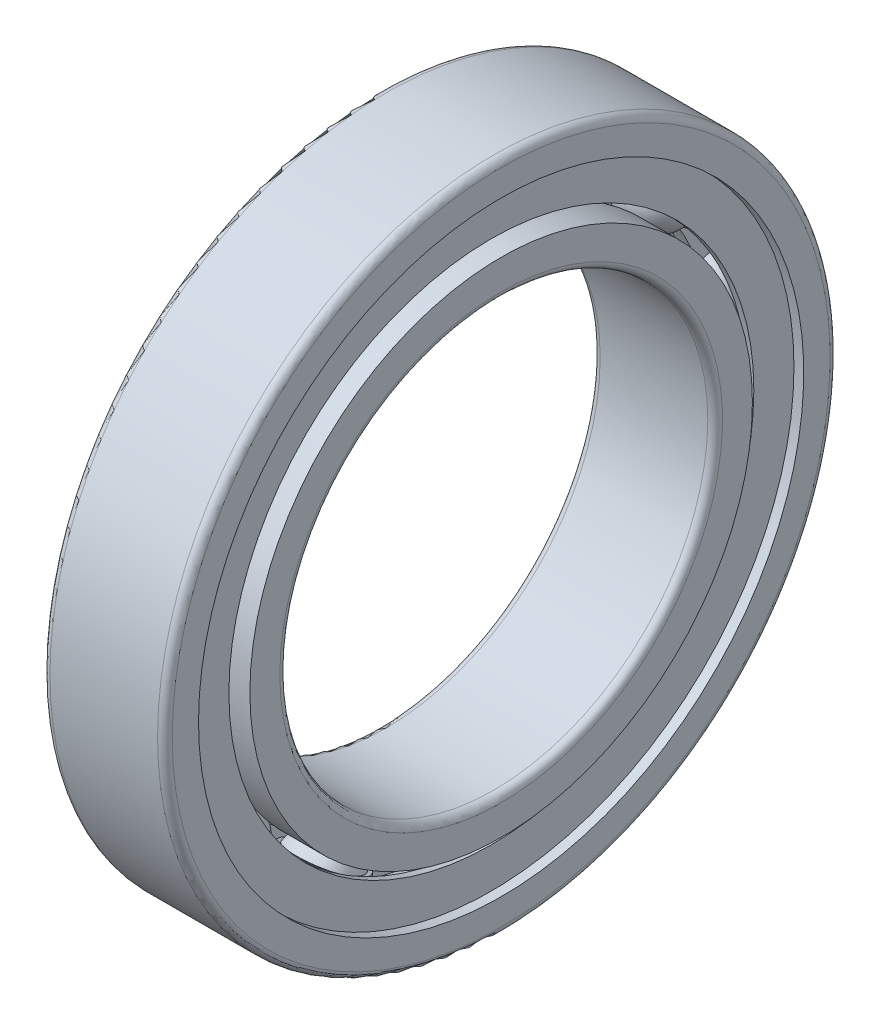
SolidWorks part; units mm, degrees
ref_plane "基准面1" through (0, 0, 0) normal (0, 0, 1) x (1, 0, 0)
ref_plane "基准面2" through (0, 0, 0) normal (0, 1, 0) x (1, 0, 0)
ref_plane "基准面3" through (0, 0, 0) normal (1, 0, 0) x (0, 0, -1)
sketch "尺寸草图" plane through (0, 0, 0) normal (0, 0, 1) x (1, 0, 0)
  point P0 (0, -75.4307)
  point P1 (5.556, -75.4307)
  point P2 (0, 50.7088)
  point P3 (35, 50.7088)
  point P4 (55, 50.7088)
  point P5 (10, 50.7088)
  point P6 (0, -10.9899)
  point P7 (41.1, -10.9899)
  point P8 (50.3, -10.9899)
  point P9 (0.6, -10.9899)
  point P10 (14, -75.4307)
  dimension "d" = 35
  dimension "DD" = 55
  dimension "B" = 10
  dimension "内圈外径DD2" = 41.1
  dimension "防尘圈径D3" = 50.3
  dimension "r" = 0.6
  dimension "球径DW" = 5.556
  dimension "球数Z" = 14
sketch "草图2" plane through (0, 0, 0) normal (0, 0, 1) x (1, 0, 0)
  line L0 (-12.4206, 0) -> (9.8128, 0) construction
  line L1 (0, 0) -> (0, 37.3563) construction
  line L2 (-5.5681, 22.65) -> (6.1049, 22.65) construction
  line L3 (-0.6112, 23.4139) -> (0.6112, 23.4139)
  line L4 (-0.6112, 23.4139) -> (-0.6112, 21.8861)
  line L5 (-0.6112, 21.8861) -> (0.6112, 21.8861)
  line L6 (0.6112, 23.4139) -> (0.6112, 21.8861)
  dimension "D1" = 1.2223
  dimension "D2" = 0.6112
  dimension "D3" = 1.5279
  dimension "D4" = 0.764
  dimension "D5" = 22.65
revolve "基体-旋转" add sketch "草图2" angle 360 about L0
sketch "草图3" plane through (0, 0, 0) normal (0, 0, 1) x (1, 0, 0)
  line L0 (-5.5681, 22.65) -> (6.1049, 22.65) construction
  line L1 (-5.5681, 22.65) -> (6.1049, 22.65) construction
  line L2 (-12.4206, 0) -> (9.8128, 0) construction
  line L3 (-12.4206, 0) -> (9.8128, 0) construction
  line L4 (0, 0) -> (0, 37.3563) construction
  line L5 (0, 0) -> (0, 37.3563) construction
  line L6 (-3.0558, 22.65) -> (3.0558, 22.65)
  arc A0 (-3.0558, 22.65) -> (3.0558, 22.65) centre (0, 22.65) ccw
  dimension "Dwww" = 6.1116
  dimension "D2" = 3.0558
revolve "凸台-旋转1" add sketch "草图3" angle 360 about L1
pattern_circular "阵列(圆周)1" count 14 over 360 about axis through (-12.4206, 0, 0) along (1, 0, 0) of "凸台-旋转1"
sketch "草图4" plane through (0, 0, 0) normal (0, 0, 1) x (1, 0, 0)
  line L0 (0, 0) -> (8.1272, 0) construction
  line L1 (-12.4206, 0) -> (9.8128, 0) construction
  line L3 (-0.6112, 23.4139) -> (0.6112, 23.4139) construction
  line L4 (-3.0558, 26.4697) -> (3.0558, 26.4698)
  line L5 (-3.0558, 26.4697) -> (-3.0558, 23.4139)
  line L6 (-3.0558, 23.4139) -> (3.0558, 23.4139)
  line L7 (3.0558, 26.4698) -> (3.0558, 23.4139)
revolve "切除-旋转1" cut sketch "草图4" angle 360 about L0
sketch "草图5" plane through (0, 0, 0) normal (0, 0, 1) x (1, 0, 0)
  line L0 (0, 0) -> (8.2665, 0) construction
  line L1 (-12.4206, 0) -> (9.8128, 0) construction
  line L2 (-0.6112, 21.8861) -> (0.6112, 21.8861) construction
  line L3 (-3.0558, 21.8861) -> (3.0558, 21.8861)
  line L4 (-3.0558, 21.8861) -> (-3.0558, 18.8302)
  line L5 (-3.0558, 18.8302) -> (3.0558, 18.8302)
  line L6 (3.0558, 21.8861) -> (3.0558, 18.8302)
revolve "切除-旋转2" cut sketch "草图5" angle 360 about L0
sketch "草图6" plane through (0, 0, 0) normal (0, 0, 1) x (1, 0, 0)
  line L0 (0, 0) -> (5.5439, 0) construction
  line L1 (-12.4206, 0) -> (9.8128, 0) construction
  line L2 (0, 0) -> (0, 11.4011) construction
  line L3 (-5.5681, 22.65) -> (6.1049, 22.65) construction
  line L4 (-5.5681, 22.65) -> (6.1049, 22.65) construction
  line L5 (-2.778, 22.65) -> (2.778, 22.65)
  arc A0 (-2.778, 22.65) -> (2.778, 22.65) centre (0, 22.65) ccw
  dimension "Dw" = 5.556
revolve "凸台-旋转2" add sketch "草图6" angle 360 about L4
pattern_circular "阵列(圆周)2" count 14 over 360 about axis through (-12.4206, 0, 0) along (1, 0, 0) of "凸台-旋转2"
sketch "草图7" plane through (0, 0, 0) normal (0, 0, 1) x (1, 0, 0)
  line L0 (0, 0) -> (6.6488, 0) construction
  line L1 (0, 0) -> (0, 16.8954) construction
  line L2 (-4.4, 27.5) -> (4.4, 27.5)
  line L3 (-5, 26.9) -> (-5, 24.75)
  line L4 (-5, 24.75) -> (-1.8033, 24.75)
  line L5 (5, 26.9) -> (5, 24.75)
  line L6 (1.8033, 24.75) -> (3.6648, 24.75)
  line L7 (4.2, 24.75) -> (5, 24.75)
  line L8 (3.6648, 25.15) -> (4.2, 25.15)
  line L9 (3.6648, 25.15) -> (3.6648, 24.75)
  line L11 (4.2, 25.15) -> (4.2, 24.75)
  arc A0 (-4.4, 27.5) -> (-5, 26.9) centre (-4.4, 26.9) ccw
  arc A1 (4.4, 27.5) -> (5, 26.9) centre (4.4, 26.9) cw
  arc A2 (2.6709, 23.4139) -> (-2.6709, 23.4139) centre (0, 22.65) ccw construction
  arc A3 (1.8186, 24.75) -> (0, 19.872) centre (0, 22.65) ccw construction
  arc A4 (1.8033, 24.75) -> (-1.8033, 24.75) centre (0, 22.65) ccw
  point P10 (-5, 27.5)
  point P13 (5, 27.5)
  dimension "R" = 0.6
  dimension "D1" = 0.01
  dimension "D2" = 49.5
  dimension "D" = 55
  dimension "D3" = 5
  dimension "B" = 10
  dimension "D4" = 0.5352
  dimension "D5" = 50.3
  dimension "D6" = 0.8
revolve "凸台-旋转3" add sketch "草图7" angle 360 about L0
sketch "草图8" plane through (0, 0, 0) normal (0, 0, 1) x (1, 0, 0)
  line L0 (-12.4206, 0) -> (9.8128, 0) construction
  line L1 (-12.4206, 0) -> (9.8128, 0) construction
  line L2 (5, 26.9) -> (5, 24.75) construction
  line L3 (-5, 20.55) -> (-1.8033, 20.55)
  line L4 (-5, 20.55) -> (-5, 18.1)
  line L5 (-4.4, 17.5) -> (4.4, 17.5)
  line L6 (5, 20.55) -> (5, 18.1)
  line L7 (-5, 26.9) -> (-5, 24.75) construction
  line L8 (1.8033, 20.55) -> (5, 20.55)
  arc A0 (-5, 18.1) -> (-4.4, 17.5) centre (-4.4, 18.1) ccw
  arc A1 (4.4, 17.5) -> (5, 18.1) centre (4.4, 18.1) ccw
  arc A2 (-2.6709, 21.8861) -> (2.6709, 21.8861) centre (0, 22.65) ccw construction
  arc A3 (-2.6709, 21.8861) -> (2.6709, 21.8861) centre (0, 22.65) ccw construction
  arc A4 (-1.8033, 20.55) -> (1.8033, 20.55) centre (0, 22.65) ccw
  dimension "D1" = 0.6
  dimension "DD" = 35
  dimension "D2" = 0.01
  dimension "DD2" = 41.1
revolve "凸台-旋转4" add sketch "草图8" angle 360 about L1
sketch "草图10" plane through (0, 0, 0) normal (0, 0, 1) x (1, 0, 0)
  line L0 (3.6648, -24.75) -> (3.6648, 24.75) construction
  line L1 (4.2, 25.15) -> (3.6648, 25.15)
  line L2 (4.2, 25.15) -> (4.2, 21.4667)
  line L3 (4.2, 21.4667) -> (3.6648, 21.4667)
  line L4 (3.6648, 25.15) -> (3.6648, 21.4667)
  line L5 (1.8033, 20.55) -> (5, 20.55) construction
  line L6 (0, 0) -> (-5.3515, 0) construction
  line L7 (-12.4206, 0) -> (9.8128, 0) construction
  dimension "D1" = 0.9167
revolve "凸台-旋转5" add sketch "草图10" angle 360 about L6
sketch "草图11" plane through (0, 0, 0) normal (1, 0, 0) x (0, 0, -1)
  circle A0 centre (0, 0) radius 27.5
  circle A1 centre (0, 0) radius 27.5 construction
extrude "切除-拉伸1" cut sketch "草图11" against normal blind 10
mirror "镜向所有1" about plane through (0, 0, 0) normal (1, 0, 0) of bodies 109
equation "\"D5@草图7\" = \"防尘圈径D3@尺寸草图\""
equation "\"Z@阵列(圆周)1\"=\"球数Z@尺寸草图\" "
equation "\"Dw@草图6\"=\"球径DW@尺寸草图\""
equation "\"DD@草图8\"=\"d@尺寸草图\""
equation "\"D@草图7\"=\"DD@尺寸草图\""
equation "\"B@草图7\"=\"B@尺寸草图\" "
equation "\"DD2@草图8\"=\"内圈外径DD2@尺寸草图\""
equation "\"R@草图7\"=\"r@尺寸草图\""
equation "\"D3@草图2\" = 0.25*\"Dwww@草图3\""
equation "\"D4@草图2\" = \"D3@草图2\"/2"
equation "\"Dwww@草图3\" = 1.1*\"Dw@草图6\""
equation "\"D2@草图3\" = 0.5*\"Dwww@草图3\""
equation "\"D1@草图2\" = 0.2*\"Dwww@草图3\""
equation "\"D2@草图2\" = 0.5*\"D1@草图2\""
equation "\"切除位置@草图4\" = \"Dwww@草图3\"/2"
equation "\"D1@阵列(圆周)2\" = \"Z@阵列(圆周)1\""
equation "\"D3@草图7\" = \"B@草图7\" / 2"
equation "\"D1@草图8\" = \"R@草图7\""
equation "\"D2@草图7\" = 0.9*\"D@草图7\""
equation "\"D5@草图2\" = 0.25* ( \"D2@草图7\" + \"DD2@草图8\" )  "
equation "\"D6@草图7\" = 0.08 * \"B@草图7\""
equation "\"D1@草图10\" = 0.15*\"Dwww@草图3\""
